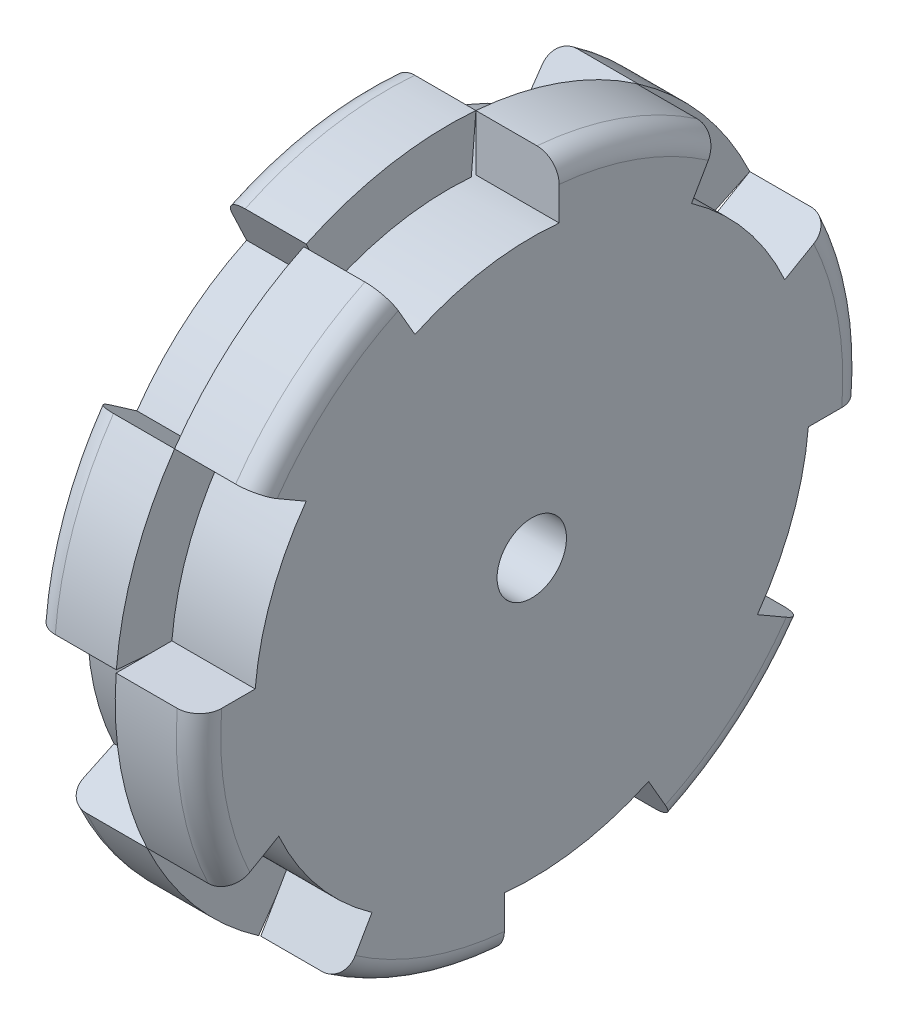
SolidWorks part; units mm, degrees
ref_plane "Front" through (0, 0, 0) normal (0, 0, 1) x (1, 0, 0)
ref_plane "Top" through (0, 0, 0) normal (0, 1, 0) x (1, 0, 0)
ref_plane "Right" through (0, 0, 0) normal (1, 0, 0) x (0, 0, -1)
sketch "Sketch1" plane through (0, 0, 0) normal (1, 0, 0) x (0, 0, -1)
  circle A0 centre (0, 0) radius 76.2
  circle A1 centre (0, 0) radius 7.9375
  dimension "D1" = 152.4
  dimension "D2" = 15.875
extrude "Boss-Extrude1" add sketch "Sketch1" along normal blind 38.1
fillet "Fillet1" radius 5.08 2 edges at (38.1, 0, -76.2) (0, 0, -76.2)
ref_plane "Bottom_Plane" through (0, 76.2, 0) normal (0, 1, 0) x (1, 0, 0)
ref_axis "Axis1" through (38.1, 0, 0) along (-1, 0, 0)
sketch "Sketch2" plane through (38.1, 0, 0) normal (1, 0, 0) x (0, 0, -1)
  line L0 (26.7091, -57.6097) -> (33.0803, -68.645)
  line L1 (-6.2684, -63.1898) -> (-6.2684, -75.9417)
  arc A0 (26.7091, -57.6097) -> (-6.2684, -63.1898) centre (0, 0) cw
  circle A1 centre (0, 0) radius 76.2 construction
  arc A2 (33.0803, -68.645) -> (-6.2684, -75.9417) centre (0, 0) cw
  dimension "D1" = 63.5
  dimension "D2" = 30
extrude "Cut-Extrude1" cut sketch "Sketch2" against normal blind 19.05
pattern_circular "CirPattern1" count 6 over 360 about axis through (33.02, 0, 0) along (-1, 0, 0) of "Cut-Extrude1"
sketch "Sketch3" plane through (0, 0, 0) normal (-1, 0, 0) x (0, 0, 1)
  line L0 (-27.1117, -57.4213) -> (-32.5341, -68.9055)
  line L1 (-52.1901, -36.1724) -> (-62.6281, -43.4069)
  arc A1 (-27.1117, -57.4213) -> (-52.1901, -36.1724) centre (0, 0) cw
  circle A2 centre (0, 0) radius 76.2 construction
  arc A3 (-32.5341, -68.9055) -> (-62.6281, -43.4069) centre (0, 0) cw
  dimension "D2" = 30
  dimension "D1" = 63.5
extrude "Cut-Extrude4" cut sketch "Sketch3" against normal blind 19.05
pattern_circular "CirPattern2" count 6 over 360 about axis through (0, 0, 0) along (-1, 0, 0) of "Cut-Extrude4"
